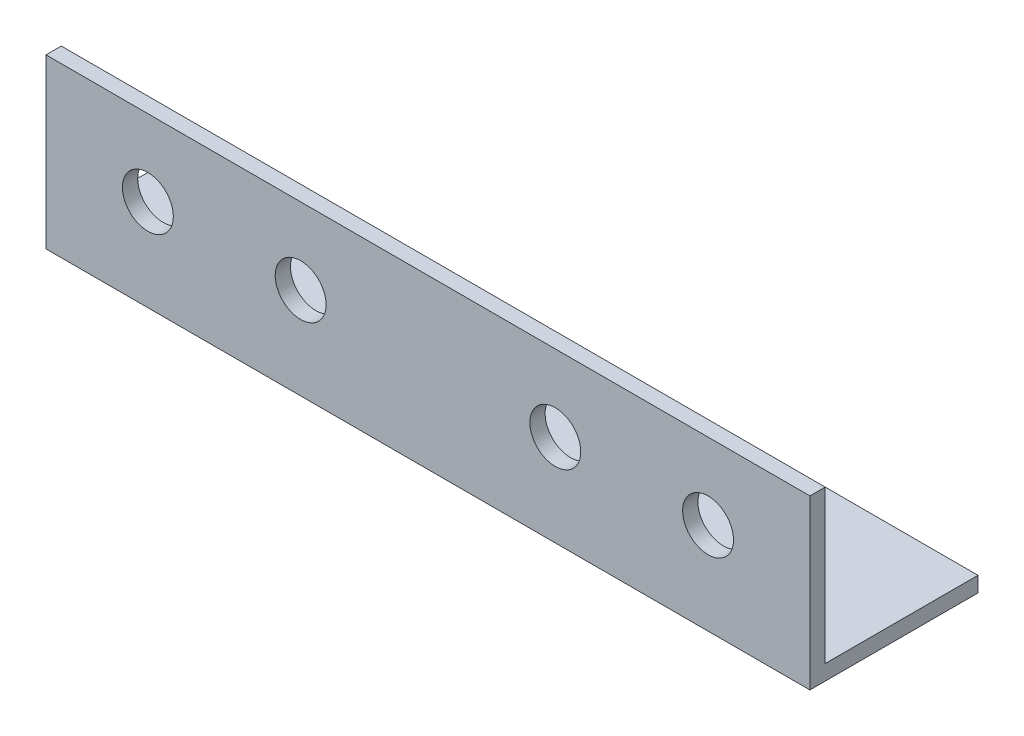
SolidWorks part; units mm, degrees
ref_plane "Спереди" through (0, 0, 0) normal (0, 0, 1) x (1, 0, 0)
ref_plane "Сверху" through (0, 0, 0) normal (0, 1, 0) x (1, 0, 0)
ref_plane "Справа" through (0, 0, 0) normal (1, 0, 0) x (0, 0, -1)
sketch "Эскиз1" plane through (0, 0, 0) normal (1, 0, 0) x (0, 0, -1)
  line L0 (0, 30) -> (0, 0)
  line L1 (0, 0) -> (30, 0)
extrude "Вытянуть-Тонкостенный1" add sketch "Эскиз1" along normal blind 150 thin thin type one direction wall 3
sketch "Эскиз2" plane through (0, 0, 0) normal (0, 0, -1) x (-1, 0, 0)
  line L0 (-75, 38.0477) -> (-75, -6) construction
  circle A0 centre (-130, 15) radius 5
  circle A1 centre (-100, 15) radius 5
  circle A2 centre (-50, 15) radius 5
  circle A3 centre (-20, 15) radius 5
  dimension "D1" = 2
extrude "Вырез-Вытянуть1" cut sketch "Эскиз2" against normal through all
